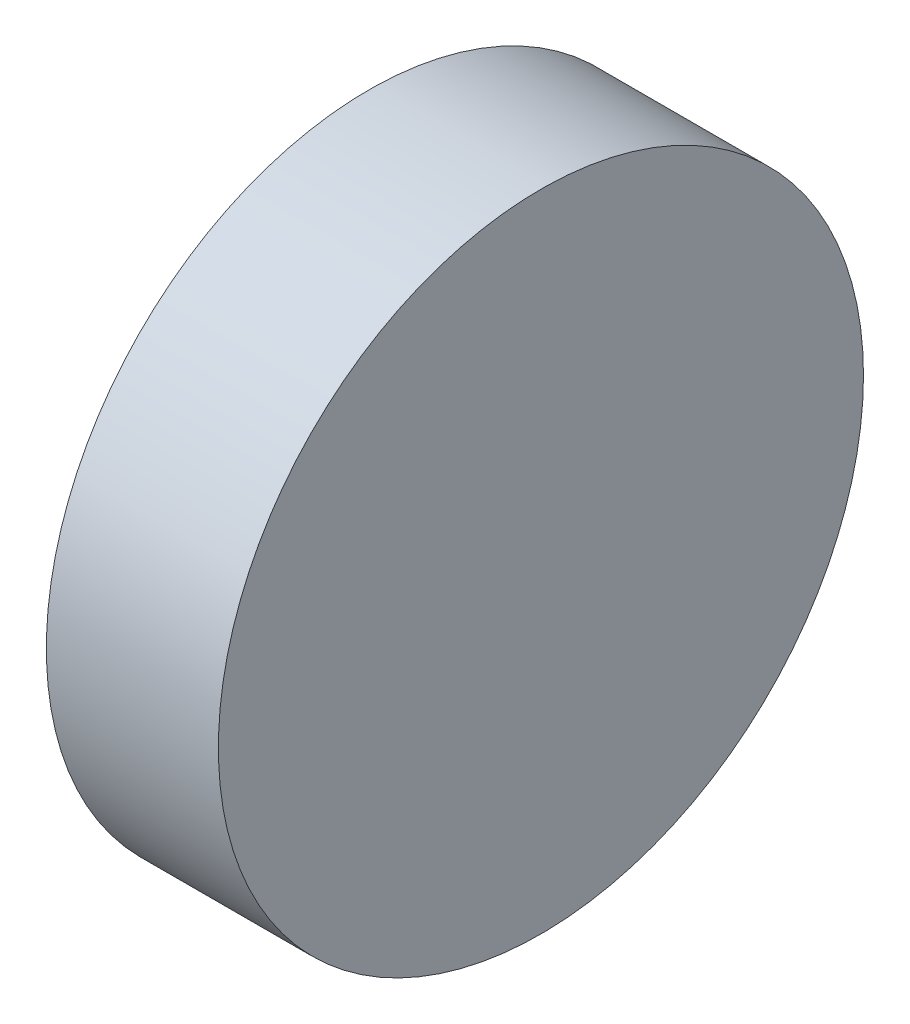
SolidWorks part; units mm, degrees
ref_plane "Front Plane" through (0, 0, 0) normal (0, 0, 1) x (1, 0, 0)
ref_plane "Top Plane" through (0, 0, 0) normal (0, 1, 0) x (1, 0, 0)
ref_plane "Right Plane" through (0, 0, 0) normal (1, 0, 0) x (0, 0, -1)
sketch "Sketch1" plane through (0, 0, 0) normal (1, 0, 0) x (0, 0, -1)
  circle A0 centre (0, 0) radius 37.5
  dimension "D1" = 75
extrude "Boss-Extrude1" add sketch "Sketch1" along normal blind 20
